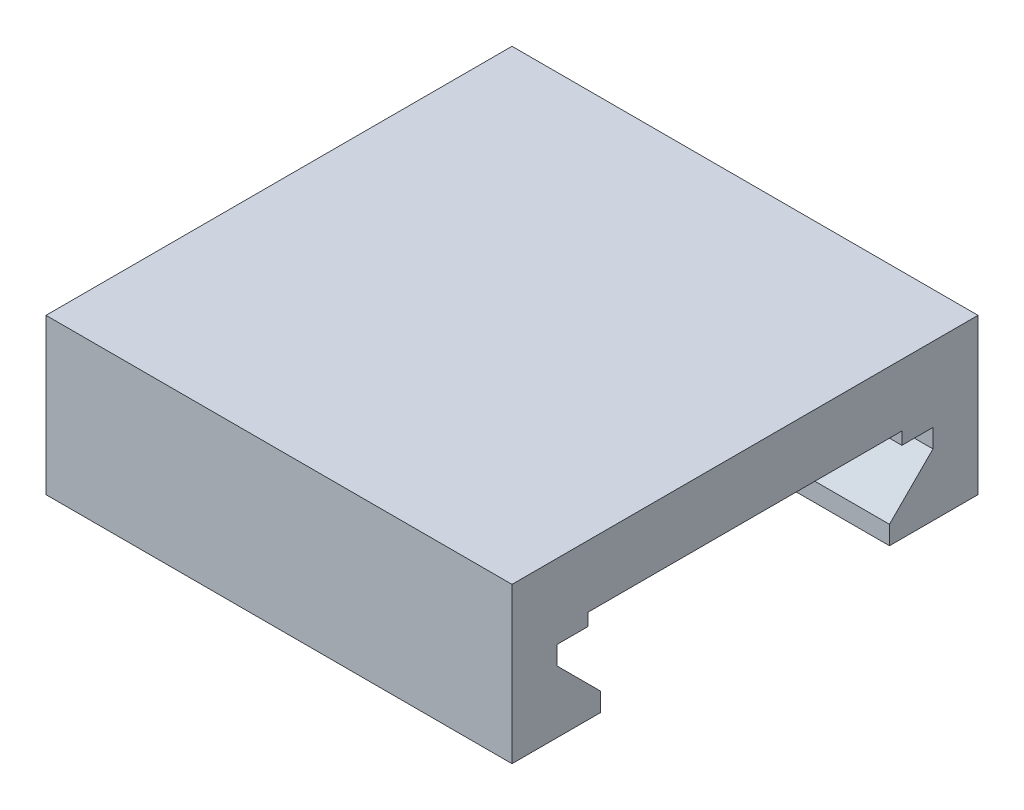
SolidWorks part; units mm, degrees
ref_plane "Front Plane" through (0, 0, 0) normal (0, 0, 1) x (1, 0, 0)
ref_plane "Top Plane" through (0, 0, 0) normal (0, 1, 0) x (1, 0, 0)
ref_plane "Right Plane" through (0, 0, 0) normal (1, 0, 0) x (0, 0, -1)
sketch "Master Design Profile" plane through (0, 0, 0) normal (1, 0, 0) x (0, 0, -1)
  line L0 (-5.05, 5.3923) -> (5.05, 5.3923)
  line L1 (12, 0) -> (6, 10.3923)
  line L2 (6, 10.3923) -> (-6, 10.3923)
  line L3 (-6, 10.3923) -> (-12, 0)
  line L4 (-12, 0) -> (-9.0156, -5.1691)
  line L5 (0, -10.3923) -> (6, -10.3923) construction
  line L6 (9.0156, -5.1691) -> (12, 0)
  line L7 (-5.05, 5.3923) -> (-5.05, 4.9923)
  line L8 (-5.05, 4.9923) -> (-6.05, 4.9923)
  line L9 (0, -28.6883) -> (0, 28.6883) construction
  line L10 (-6.05, 4.9923) -> (-6.05, 4.3923)
  line L11 (-6.05, 4.3923) -> (-4.65, 2.9923)
  line L13 (-4.65, 2.9923) -> (-4.65, 2.3923)
  line L14 (-4.65, 2.3923) -> (-9.0156, -5.1691)
  line L15 (4.65, 2.3923) -> (9.0156, -5.1691)
  line L16 (4.65, 2.9923) -> (4.65, 2.3923)
  line L17 (6.05, 4.3923) -> (4.65, 2.9923)
  line L18 (6.05, 4.9923) -> (6.05, 4.3923)
  line L19 (5.05, 4.9923) -> (6.05, 4.9923)
  line L20 (5.05, 5.3923) -> (5.05, 4.9923)
  line L21 (-9, -5.1962) -> (-6, -10.3923) construction
  line L22 (-9.0156, -5.1691) -> (-9, -5.1962) construction
  line L23 (-6, -10.3923) -> (0, -10.3923) construction
  line L24 (6, -10.3923) -> (9, -5.1962) construction
  line L25 (9, -5.1962) -> (9.0156, -5.1691) construction
  circle A0 centre (0, 0) radius 10.3923 construction
  point P15 (0, 0)
  point P16 (0, 5.3923)
  dimension "D1" = 10.1
  dimension "D2" = 0.4
  dimension "D3" = 0.6
  dimension "D4" = 1
  dimension "D5" = 135
  dimension "D6" = 2
  dimension "D7" = 5
  dimension "D8" = 210
  dimension "D9" = 0.6
  dimension "D10" = 12
sketch "LED Groove Profile Test" plane through (0, 0, 0) normal (1, 0, 0) x (0, 0, -1)
  line L0 (4.65, 2.9923) -> (4.65, 2.3923) construction
  line L1 (6.05, 4.3923) -> (4.65, 2.9923) construction
  line L2 (6.05, 4.9923) -> (6.05, 4.3923) construction
  line L3 (5.05, 4.9923) -> (6.05, 4.9923) construction
  line L4 (5.05, 5.3923) -> (5.05, 4.9923) construction
  line L5 (-5.05, 5.3923) -> (5.05, 5.3923) construction
  line L6 (-5.05, 5.3923) -> (-5.05, 4.9923) construction
  line L7 (-5.05, 4.9923) -> (-6.05, 4.9923) construction
  line L8 (-6.05, 4.9923) -> (-6.05, 4.3923) construction
  line L9 (-6.05, 4.3923) -> (-4.65, 2.9923) construction
  line L10 (-4.65, 2.9923) -> (-4.65, 2.3923) construction
  line L11 (-4.65, 2.9923) -> (-4.65, 2.3923)
  line L12 (-6.05, 4.3923) -> (-4.65, 2.9923)
  line L13 (-6.05, 4.9923) -> (-6.05, 4.3923)
  line L14 (-5.05, 4.9923) -> (-6.05, 4.9923)
  line L15 (-5.05, 5.3923) -> (-5.05, 4.9923)
  line L16 (-5.05, 5.3923) -> (5.05, 5.3923)
  line L17 (5.05, 5.3923) -> (5.05, 4.9923)
  line L18 (5.05, 4.9923) -> (6.05, 4.9923)
  line L19 (6.05, 4.9923) -> (6.05, 4.3923)
  line L20 (6.05, 4.3923) -> (4.65, 2.9923)
  line L21 (4.65, 2.9923) -> (4.65, 2.3923)
  line L22 (-4.65, 2.3923) -> (-7.5, 2.3923)
  line L23 (-7.5, 2.3923) -> (-7.5, 7.3923)
  line L24 (-7.5, 7.3923) -> (7.5, 7.3923)
  line L25 (7.5, 7.3923) -> (7.5, 2.3923)
  line L26 (7.5, 2.3923) -> (4.65, 2.3923)
  line L27 (0, -28.6883) -> (0, 28.6883) construction
  point P0 (0, 7.3923)
  dimension "D1" = 5
  dimension "D2" = 15
extrude "Boss-Extrude1" add sketch "LED Groove Profile Test" along normal mid plane 15
